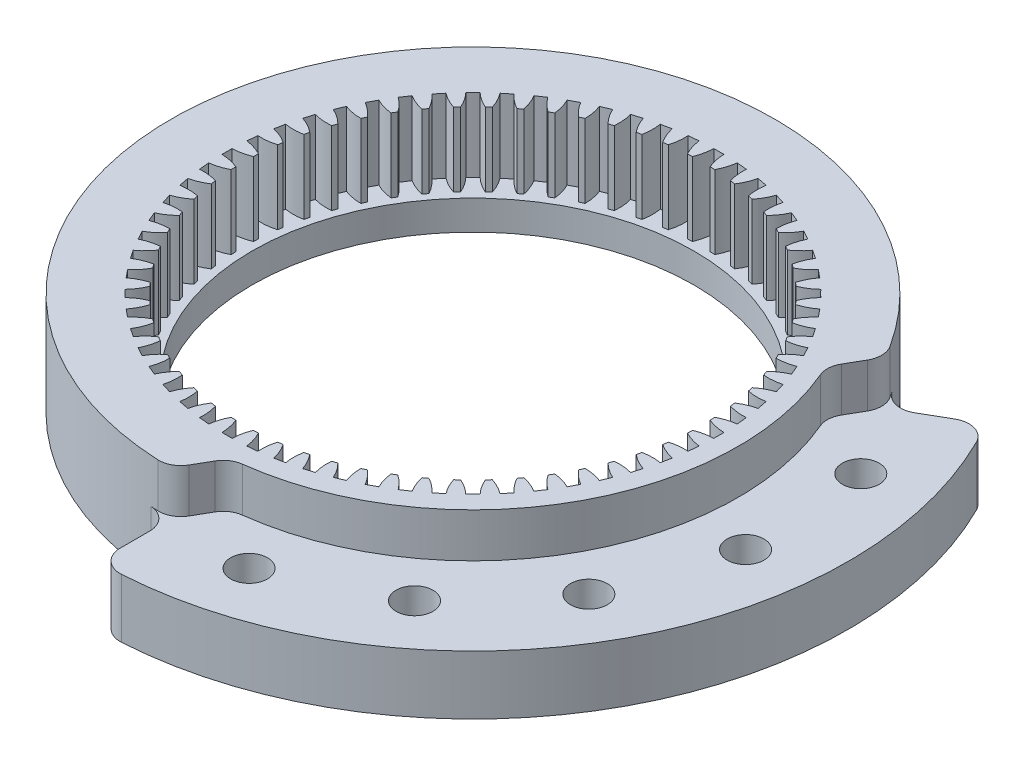
SolidWorks part; units mm, degrees
material "eSUN Tough Resin"
ref_plane "Front Plane" through (0, 0, 0) normal (0, 0, 1) x (1, 0, 0)
ref_plane "Top Plane" through (0, 0, 0) normal (0, 1, 0) x (1, 0, 0)
ref_plane "Right Plane" through (0, 0, 0) normal (1, 0, 0) x (0, 0, -1)
sketch "Sketch1" plane through (0, 0, 0) normal (0, 1, 0) x (1, 0, 0)
  circle A0 centre (0, 0) radius 16
  circle A1 centre (0, 0) radius 16.7
  circle A2 centre (0, 0) radius 15.5
  dimension "D1" = 32
  dimension "D2" = 33.4
  dimension "D3" = 1.2
extrude "Boss-Extrude1" add sketch "Sketch1" along normal mid plane 5 contours A1 A0 | A0 A2 | A2 region at (-15.5475, 0, 0) region at (-16.2277, 0, 0) region at (0, 0, 0)
sketch "Sketch7" plane through (0, 0, 0) normal (0, 1, 0) x (1, 0, 0)
  line L0 (16.7, 0) -> (-16.7, 0) construction
  line L1 (0, 16.7) -> (0, -16.7) construction
  circle A0 centre (0, 0) radius 16.7 construction
  point P7 (0, 0)
sketch "Sketch4" plane through (0, 0, 0) normal (0, 1, 0) x (1, 0, 0)
  line L0 (0, 0) -> (0, -25.5) construction
  line L10 (0, 0) -> (22.0836, 12.75) construction
  line L11 (22.0836, 12.75) -> (17.7535, 10.25)
  line L12 (0, -25.5) -> (0, -20.5)
  circle A2 centre (0, 0) radius 15.5 construction
  circle A3 centre (0, 0) radius 15.5
  arc A4 (17.7535, 10.25) -> (0, -20.5) centre (0, 0) ccw
  circle A9 centre (0, 0) radius 25.5 construction
  arc A10 (22.0836, 12.75) -> (0, -25.5) centre (0, 0) cw
  dimension "D1" = 5
  dimension "D3" = 120
  dimension "D2" = 5
extrude "Boss-Extrude2" add sketch "Sketch4" along normal mid plane 5
sketch "Sketch3" plane through (0, 0, 0) normal (0, 1, 0) x (1, 0, 0)
  line L0 (0, 0) -> (0, 16.7) construction
  line L1 (-0.3927, 15.9952) -> (0.3927, 15.9952) construction
  line L2 (-0.3434, 15.4962) -> (0, 0) construction
  line L3 (0, 13.7683) -> (-0.5155, 16.692) construction
  line L4 (0, 0) -> (0.8194, 16.6799) construction
  line L5 (0.3927, 15.9952) -> (1.177, 15.9566) construction
  line L6 (0, 15.5) -> (0, 16.7) construction
  line L7 (0.3434, 15.4962) -> (0.3434, 16.7) construction
  line L8 (0.3434, 16.0981) -> (-0.3121, 16.0981) construction
  arc A1 (-0.5957, 16.6894) -> (-0.3434, 15.4962) centre (-3.6364, 15.4232) cw construction
  arc A2 (0.5957, 16.6894) -> (0.3434, 15.4962) centre (3.6364, 15.4232) ccw construction
  circle A3 centre (0, 0) radius 15.5 construction
  arc A4 (0.3434, 15.4962) -> (-0.3434, 15.4962) centre (0, 0) ccw construction
  circle A5 centre (0, 0) radius 16 construction
  circle A6 centre (0, 0) radius 16.7 construction
  arc A7 (0.5957, 15.5068) -> (-0.5957, 15.5068) centre (0, 32.1962) cw
  arc A8 (0.5957, 16.6894) -> (-0.5957, 16.6894) centre (0, 0) ccw construction
  arc A9 (-0.5957, 15.5068) -> (-0.3434, 16.7) centre (-3.6364, 16.773) ccw
  arc A10 (0.5957, 15.5068) -> (0.3434, 16.7) centre (3.6364, 16.773) cw
  arc A11 (0.3434, 16.7) -> (-0.3434, 16.7) centre (0, 32.1962) cw
  dimension "D3" = 2.813
  dimension "D2" = 10
extrude "Cut-Extrude1" cut sketch "Sketch3" against normal through all both and the other way through all
pattern_circular "CirPattern1" count 64 over 360 about axis through (0, 2.5, 0) along (0, 1, 0) of "Cut-Extrude1"
sketch "Sketch5" plane through (0, 0, 0) normal (0, 1, 0) x (1, 0, 0)
  circle A0 centre (0, 0) radius 15.5183
extrude "Cut-Extrude2" cut sketch "Sketch5" against normal through all both and the other way through all
sketch "Sketch8" plane through (0, -2.5, 0) normal (0, -1, 0) x (1, 0, 0)
  line L2 (0, 25.5) -> (0, 20.5)
  line L6 (0, 25.5) -> (0, 20.5)
  line L8 (17.7535, -10.25) -> (22.0836, -12.75)
  line L9 (17.7535, -10.25) -> (22.0836, -12.75)
  circle A0 centre (0, 0) radius 15
  arc A3 (22.0836, -12.75) -> (0, 25.5) centre (0, 0) ccw
  arc A4 (22.0836, -12.75) -> (0, 25.5) centre (0, 0) ccw
  arc A5 (0, 20.5) -> (17.7535, -10.25) centre (0, 0) ccw
  arc A7 (0, 20.5) -> (17.7535, -10.25) centre (0, 0) ccw
  dimension "D2" = 30
  dimension "D1" = 0
extrude "Boss-Extrude3" add sketch "Sketch8" along normal blind 2
sketch "Sketch6" plane through (0, 2.5, 0) normal (0, 1, 0) x (1, 0, 0)
  line L0 (0, 0) -> (5.5646, -20.7674) construction
  line L2 (0, -16.7) -> (0, 16.7) construction
  circle A3 centre (5.5646, -20.7674) radius 0.5
  point P11 (0, 0)
  dimension "D2" = 15
  dimension "D1" = 1
  dimension "D3" = 21.5
extrude "Cut-Extrude3" cut sketch "Sketch6" against normal through all
pattern_circular "CirPattern2" count 5 every 22.5 about axis through (0, -2.5, 0) along (0, -1, 0) of "Cut-Extrude3" reverse direction yes
sketch "Sketch9" plane through (0, 2.5, 0) normal (0, 1, 0) x (1, 0, 0)
  line L0 (17.7535, 10.25) -> (16.275, 7.6892)
  line L1 (0, -20.5) -> (1.4785, -17.9392)
  line L2 (0, 0) -> (18.6195, -10.75) construction
  line L3 (1.4785, -17.9392) -> (16.275, 7.6892) construction
  line L4 (17.7535, 10.25) -> (22.0836, 12.75)
  line L5 (0, -20.5) -> (0, -25.5)
  arc A0 (1.4785, -17.9392) -> (16.275, 7.6892) centre (0, 0) ccw
  arc A1 (0, -25.5) -> (22.0836, 12.75) centre (0, 0) ccw construction
  arc A2 (0, -25.5) -> (22.0836, 12.75) centre (0, 0) ccw
  point P5 (8.8768, -5.125)
  dimension "D1" = 36
extrude "Cut-Extrude4" cut sketch "Sketch9" against normal offset from surface (3 mm away) 4 up to face at (13.2797, -4.5, 17.519)
fillet "Fillet1" radius 1.5 6 edges at (17.7535, -2.5, -10.25) (22.0836, -2.5, -12.75) (0, -2.5, 25.5) (0, -2.5, 20.5) (16.275, 1, -7.6892) (1.4785, 1, 17.9392)
fillet "Fillet2" radius 1.5 2 edges at (0, 1, 20.5) (17.7535, 1, -10.25)
hole_wizard "Ø2.5mm Dowel Hole1" positions "Sketch12" profile "Sketch11" hole size "Ø2.5" standard "ISO"
sketch "Sketch12" plane through (0, -4.5, 0) normal (0, -1, 0) x (-1, 0, 0)
  point P0 (-5.5646, -20.7674)
  point P3 (-13.0884, -17.0571)
  point P6 (-18.6195, -10.75)
  point P9 (-21.3161, -2.8063)
  point P12 (-20.7674, 5.5646)
sketch "Sketch11" plane through (5.5646, -4.5, 20.7674) normal (1, 0, 0) x (0, 0, -1)
  line L0 (0, 0) -> (0, 4.7511)
  line L1 (0, 4.7511) -> (1.25, 4)
  line L2 (1.25, 4) -> (1.25, 0)
  line L5 (1.25, 0) -> (0, 0)
  line L10 (0, 4.7511) -> (-1.25, 4) construction
  line L11 (0, -6.35) -> (0, 107.95) construction
  dimension "Hole Dia." = 2.5
  dimension "Hole Depth" = 4
  dimension "Drill Angle" = 118
ref_axis "Axis2" through (0, -4.5, 0) along (0, 1, 0)
ref_plane "Plane1" through (0, 0, 0) normal (-0.5, 0, 0.866) x (0.866, 0, 0.5)
equation "\"Module\"= .5"
equation "\"Number of Teeth\"=64"
equation "\"D1@Sketch1\"=\"Module\"* \"Number of Teeth\""
equation "\"D2@Sketch1\"=(\"Number of Teeth\" + 2) * \"Module\" + .4"
equation "\"D3@Sketch1\"=\"Module\" * if( \"Module\" => 1.25, 2.25, 2.4)"
equation "\"D3@Sketch3\"=180 / \"Number of Teeth\""
equation "\"D1@CirPattern1\"=\"Number of Teeth\""
